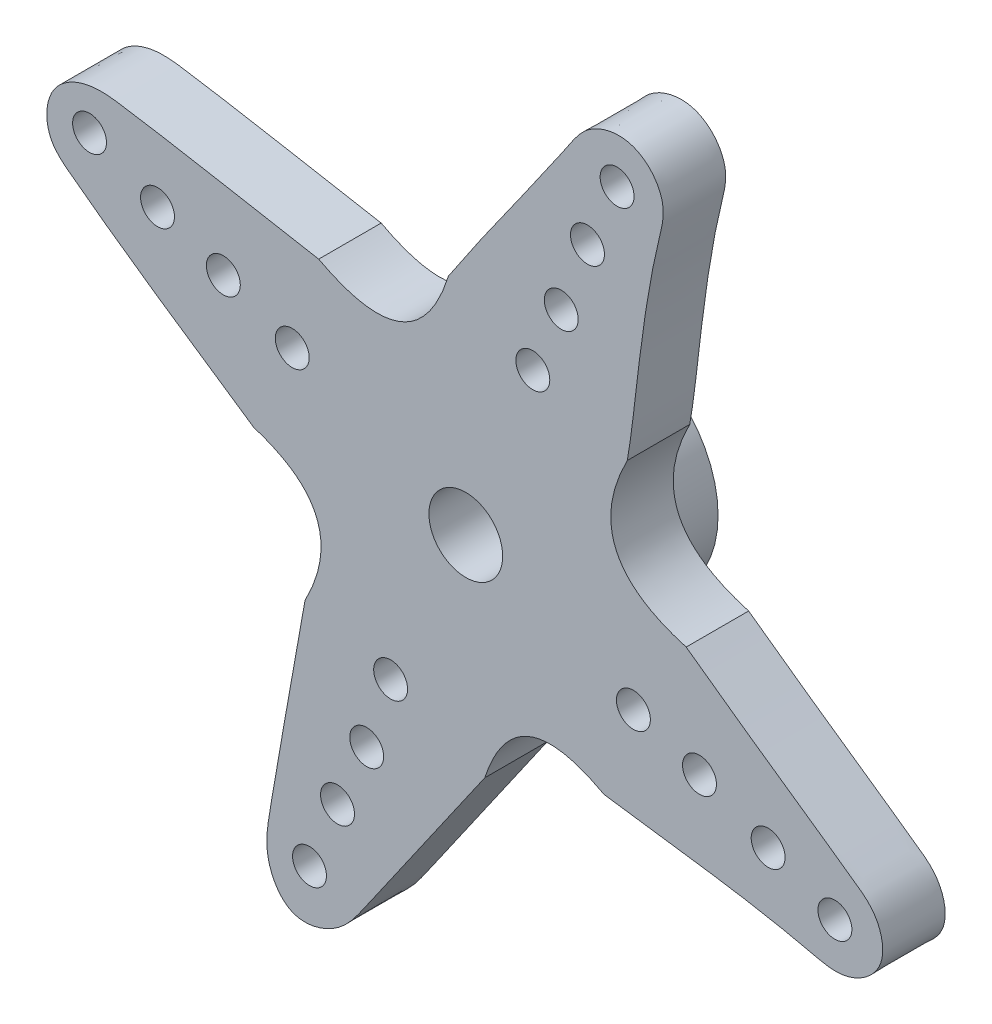
SolidWorks part; units mm, degrees
ref_plane "Front Plane" through (0, 0, 0) normal (0, 0, 1) x (1, 0, 0)
ref_plane "Top Plane" through (0, 0, 0) normal (0, 1, 0) x (1, 0, 0)
ref_plane "Right Plane" through (0, 0, 0) normal (1, 0, 0) x (0, 0, -1)
sketch "Esquisse1" plane through (0, 0, 0) normal (0, 0, 1) x (1, 0, 0)
  line L0 (-122.247, 39.8956) -> (-38.7094, 41.2028) construction
  line L1 (-36.111, -44.6548) -> (67.3608, -4.9357) construction
  circle A1 centre (0, 0) radius 1.5
  circle A2 centre (-3.0557, -6.6157) radius 0.6896
  circle A3 centre (6.8165, -2.7504) radius 0.6896
  circle A4 centre (9.5038, -3.694) radius 0.6896
  circle A5 centre (12.2964, -4.8679) radius 0.6896
  circle A6 centre (15.011, -6.0447) radius 0.6896
  circle A7 centre (2.7259, 7.1664) radius 0.6896
  circle A8 centre (3.8821, 9.8731) radius 0.6896
  circle A9 centre (4.9483, 12.7008) radius 0.6896
  circle A10 centre (6.1536, 15.3431) radius 0.6896
  circle A11 centre (-4.0293, -9.4824) radius 0.6896
  circle A12 centre (-5.2157, -12.0968) radius 0.6896
  circle A13 centre (-6.3552, -14.8372) radius 0.6896
  circle A14 centre (-7.0574, 3.0555) radius 0.6896
  circle A15 centre (-9.8592, 4.2163) radius 0.6896
  circle A16 centre (-12.5358, 5.2796) radius 0.6896
  circle A17 centre (-15.3, 6.5107) radius 0.6896
  circle A18 centre (0, 0) radius 4.44
  spline S0 degree 2 poles (6.5671, 5.9054) (4.4618, 1.8281) (8.9627, 0.5332) knots 0 0 0 1 1 1
  spline S1 degree 3 poles (-0.7032, 8.7681) (1.0381, 11.4146) (2.7263, 13.6002) (4.9858, 17.0287) (6.945, 17.4757) (8.2492, 15.842) (7.1237, 11.6665) (6.9128, 7.7956) (6.5671, 5.9054) knots 0 0 0 0 0.368171 0.418118 0.499474 0.581227 0.63128 1 1 1 1
  spline S2 degree 2 poles (-0.7032, 8.7681) (-2.0086, 4.6056) (-5.9806, 6.7238) knots 0 0 0 1 1 1
  spline S3 degree 3 poles (8.9627, 0.5332) (11.2336, -1.1352) (13.7943, -2.872) (16.8047, -5.0199) (17.2405, -6.8791) (15.534, -8.0539) (11.4593, -7.033) (8.2548, -6.7291) (5.6258, -6.3293) knots 0 0 0 0 0.365231 0.41369 0.484595 0.573039 0.62458 1 1 1 1
  spline S4 degree 2 poles (5.6258, -6.3293) (2.0249, -4.3441) (0.7716, -8.1669) knots 0 0 0 1 1 1
  spline S5 degree 3 poles (0.7716, -8.1669) (-1.4985, -11.4059) (-2.5721, -12.9916) (-5.1349, -16.6354) (-7.2484, -17.3265) (-8.2346, -15.3841) (-7.5607, -11.1542) (-7.169, -9.214) (-6.5382, -5.5749) knots 0 0 0 0 0.370191 0.421117 0.509255 0.593778 0.642852 1 1 1 1
  spline S6 degree 2 poles (-6.5382, -5.5749) (-4.5484, -1.7908) (-8.6251, -0.5232) knots 0 0 0 1 1 1
  spline S7 degree 3 poles (-8.6251, -0.5232) (-12.0915, 1.8255) (-13.6557, 2.852) (-17.125, 5.4629) (-17.083, 7.5179) (-15.3867, 8.352) (-11.0921, 7.6793) (-8.6993, 7.1951) (-5.9806, 6.7238) knots 0 0 0 0 0.388588 0.439956 0.513686 0.605056 0.653688 1 1 1 1
  point P38 (-6.0676, -2.4138)
  point P42 (-6.5382, -5.5749)
  point P46 (-8.6251, -0.5232)
  point P49 (-5.9806, 6.7238)
  point P50 (-0.7032, 8.7681)
  point P51 (6.5671, 5.9054)
  point P52 (8.9627, 0.5332)
  point P53 (6.0045, 2.5837)
  point P54 (0, 0)
  point P56 (6.0744, 2.6164)
  point P57 (0, 0)
  point P60 (6.309, -6.3219)
  point P63 (0, 0)
  point P66 (2.422, -5.7973)
  point P67 (0, 0)
  point P68 (5.7354, -6.3544)
  point P71 (5.474, -7.0203)
  point P74 (5.6258, -6.3293)
  point P77 (2.7259, -5.7989)
  point P80 (0, 0)
  point P83 (0, 0)
  point P84 (3.3059, -7.0322)
  point P85 (2.5231, -5.832)
  point P86 (0, 0)
extrude "Boss.-Extru.4" add sketch "Esquisse1" along normal blind 2.54 contours S0 S3 S4 S5 S6 S7 S2 S1 | A2 | A11 | A12 | A13 | A14 | A15 | A16 | A17 | A7 | A8 | A9 | A10 | A3 | A4 | A5 | A6 | A1
extrude "Boss.-Extru.7" add sketch "Esquisse1<7>" against normal blind 3.28 contours A1 | A18
sketch "Esquisse1<7>" plane through (0, 0, 0) normal (0, 0, 1) x (1, 0, 0) same geometry as "Esquisse1"
